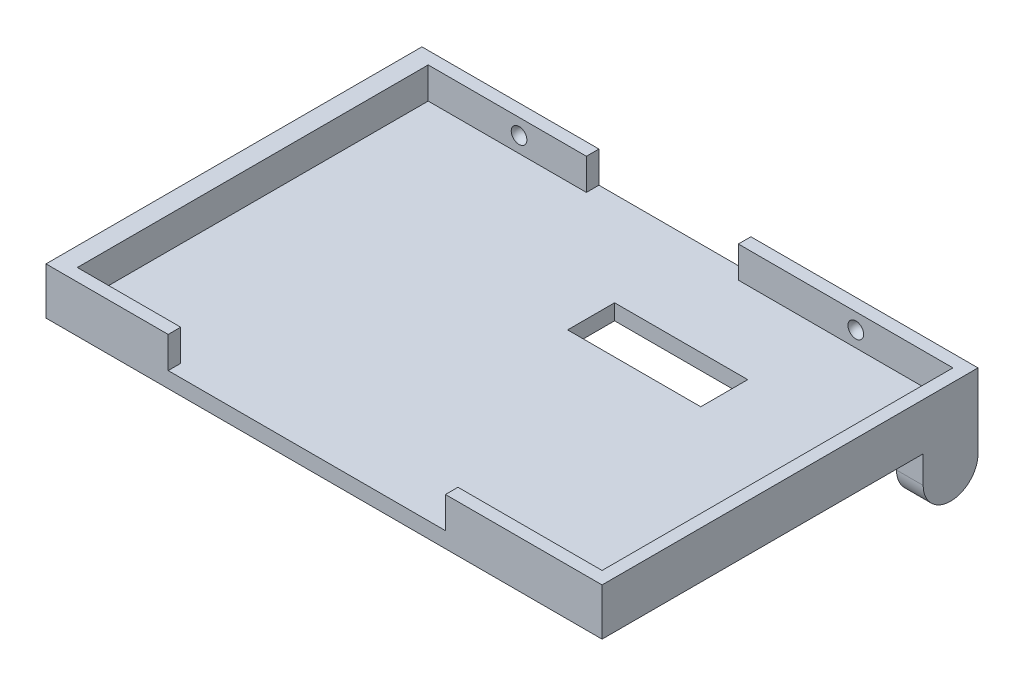
SolidWorks part; units mm, degrees
ref_plane "前视基准面" through (0, 0, 0) normal (0, 0, 1) x (1, 0, 0)
ref_plane "上视基准面" through (0, 0, 0) normal (0, 1, 0) x (1, 0, 0)
ref_plane "右视基准面" through (0, 0, 0) normal (1, 0, 0) x (0, 0, -1)
sketch "草图1" plane through (0, 0, 0) normal (0, 1, 0) x (1, 0, 0)
  line L1 (-17.75, 12) -> (17.75, 12)
  line L2 (-17.75, 12) -> (-17.75, -12)
  line L3 (-17.75, -12) -> (17.75, -12)
  line L4 (17.75, 12) -> (17.75, -12)
  line L5 (-17.75, 12) -> (17.75, -12) construction
  line L6 (-17.75, -12) -> (17.75, 12) construction
  point P0 (0, 0)
  dimension "D1" = 24
  dimension "D2" = 35.5
extrude "凸台-拉伸1" add sketch "草图1" along normal blind 3
sketch "草图2" plane through (0, 3, 0) normal (0, 1, 0) x (1, 0, 0)
  line L0 (17.75, 12) -> (-17.75, 12) construction
  line L1 (-15.75, 10) -> (15.75, 10)
  line L2 (-15.75, 10) -> (-15.75, -10)
  line L3 (-15.75, -10) -> (15.75, -10)
  line L4 (15.75, 10) -> (15.75, -10)
  line L5 (-15.75, 10) -> (15.75, -10) construction
  line L6 (-15.75, -10) -> (15.75, 10) construction
  line L7 (-17.75, 12) -> (-17.75, -12) construction
  point P0 (0, 0)
  dimension "D1" = 2
  dimension "D2" = 2
extrude "切除-拉伸1" cut sketch "草图2" against normal blind 2
sketch "草图4" plane through (0, 0, 0) normal (0, -1, 0) x (1, 0, 0)
  line L1 (-17.75, -12) -> (-16.05, -12)
  line L2 (-17.75, -12) -> (-17.75, -8.5)
  line L3 (-17.75, -8.5) -> (-16.05, -8.5)
  line L4 (-16.05, -12) -> (-16.05, -8.5)
  line L5 (17.75, -12) -> (16.05, -12)
  line L6 (17.75, -12) -> (17.75, -8.5)
  line L7 (17.75, -8.5) -> (16.05, -8.5)
  line L8 (16.05, -12) -> (16.05, -8.5)
  dimension "D1" = 3.5
  dimension "D2" = 1.7
  dimension "D3" = 1.7
  dimension "D4" = 3.5
extrude "凸台-拉伸2" add sketch "草图4" along normal blind 3.5
sketch "草图5" plane through (-17.75, 0, 0) normal (-1, 0, 0) x (0, 0, 1)
  line L1 (-12, 3) -> (-12, -3.5) construction
  line L2 (-12, -1.75) -> (-12, -3.5)
  line L5 (-10.25, -3.5) -> (-12, -3.5)
  arc A1 (-12, -1.75) -> (-10.25, -3.5) centre (-10.25, -1.75) ccw
  dimension "D1" = 1.75
extrude "切除-拉伸3" cut sketch "草图5" against normal blind 2
sketch "草图6" plane through (-17.75, 0, 0) normal (-1, 0, 0) x (0, 0, 1)
  line L0 (-8.5, -3.5) -> (-10.25, -3.5)
  line L1 (-8.5, -3.5) -> (-10.25, -3.5) construction
  line L2 (-8.5, -3.5) -> (-8.5, 0) construction
  line L3 (-8.5, -3.5) -> (-8.5, -1.75)
  arc A0 (-12, -1.75) -> (-10.25, -3.5) centre (-10.25, -1.75) ccw construction
  arc A1 (-10.25, -3.5) -> (-8.5, -1.75) centre (-10.25, -1.75) ccw
extrude "切除-拉伸4" cut sketch "草图6" against normal blind 2
sketch "草图7" plane through (17.75, 0, 0) normal (1, 0, 0) x (0, 0, -1)
  line L0 (8.5, -3.5) -> (10.25, -3.5)
  line L1 (12, -3.5) -> (8.5, -3.5) construction
  line L2 (8.5, -3.5) -> (8.5, 0) construction
  line L3 (8.5, -1.75) -> (8.5, -3.5)
  arc A0 (10.25, -3.5) -> (8.5, -1.75) centre (10.25, -1.75) cw
extrude "切除-拉伸5" cut sketch "草图7" against normal blind 2
sketch "草图8" plane through (17.75, 0, 0) normal (1, 0, 0) x (0, 0, -1)
  line L0 (12, -3.5) -> (10.25, -3.5)
  line L1 (12, 3) -> (12, -3.5) construction
  line L2 (12, -1.75) -> (12, -3.5)
  arc A0 (10.25, -3.5) -> (12, -1.75) centre (10.25, -1.75) ccw
extrude "切除-拉伸6" cut sketch "草图8" against normal blind 2
sketch "草图10" plane through (16.05, 0, 0) normal (-1, 0, 0) x (0, 0, 1)
  line L0 (-8.5, -1.75) -> (-8.5, 0) construction
  line L1 (12, 0) -> (-8.5, 0) construction
  circle A0 centre (-10.25, -1.75) radius 0.6
  dimension "D1" = 1.2
  dimension "D2" = 1.75
  dimension "D3" = 1.75
extrude "切除-拉伸8" cut sketch "草图10" against normal blind 1.5
sketch "草图11" plane through (0, 0, 0) normal (0, -1, 0) x (1, 0, 0)
  line L1 (0.55, -3) -> (9.05, -3)
  line L2 (0.55, -3) -> (0.55, -6)
  line L3 (0.55, -6) -> (9.05, -6)
  line L4 (9.05, -3) -> (9.05, -6)
  line L5 (16.05, -8.5) -> (16.05, -12) construction
  line L6 (16.05, -12) -> (-16.05, -12) construction
  dimension "D1" = 7
  dimension "D2" = 8.5
  dimension "D3" = 3
  dimension "D4" = 6
extrude "切除-拉伸9" cut sketch "草图11" against normal blind 2
sketch "草图12" plane through (-16.05, 0, 0) normal (1, 0, 0) x (0, 0, -1)
  line L0 (12, -1.75) -> (12, 0) construction
  line L1 (12, 0) -> (8.5, 0) construction
  circle A0 centre (10.25, -1.75) radius 0.6
  dimension "D1" = 1.2
  dimension "D2" = 1.75
  dimension "D3" = 1.75
extrude "切除-拉伸10" cut sketch "草图12" against normal blind 1.5
sketch "草图13" plane through (0, 3, 0) normal (0, 1, 0) x (1, 0, 0)
  line L1 (-15.6782, 11.2) -> (16.95, 11.2)
  line L2 (16.95, 11.2) -> (16.95, -11.2)
  line L3 (16.95, -11.2) -> (-15.75, -11.2)
  line L10 (17.75, -12) -> (17.75, 12) construction
  line L11 (-17.75, -12) -> (17.75, -12) construction
  line L12 (-15.6782, 11.2) -> (-16.55, 11.2)
  line L13 (-16.55, 11.2) -> (-16.55, -11.2)
  line L14 (-16.55, -11.2) -> (-15.75, -11.2)
  line L15 (-17.75, 12) -> (-17.75, -12) construction
  dimension "D1" = 1.2
  dimension "D2" = 0.8
  dimension "D3" = 0.8
extrude "切除-拉伸11" cut sketch "草图13" against normal blind 2
sketch "草图14" plane through (0, 0, -11.2) normal (0, 0, 1) x (1, 0, 0)
  line L0 (16.95, 1) -> (-16.55, 1) construction
  line L2 (-17.75, 3) -> (-17.75, -1.75) construction
  line L3 (-11.25, 2) -> (-10.25, 2)
  line L5 (10.25, 2) -> (11.25, 2)
  line L7 (17.75, 3) -> (17.75, -1.75) construction
  arc A2 (-11.25, 2) -> (-10.25, 2) centre (-10.75, 2) cw
  arc A3 (10.25, 2) -> (11.25, 2) centre (10.75, 2) cw
  dimension "D1" = 7
  dimension "D4" = 1
  dimension "D7" = 0.5
  dimension "D6" = 0.5
  dimension "D2" = 1
  dimension "D3" = 1
  dimension "D5" = 1
  dimension "D8" = 7
revolve "切除-旋转1" cut sketch "草图14" angle 360 about L5
sketch "草图15" plane through (0, 0, 11.2) normal (0, 0, -1) x (-1, 0, 0)
  line L0 (10.25, 2) -> (11.25, 2)
  line L1 (16.55, 1) -> (-16.95, 1) construction
  line L3 (-11.25, 2) -> (-10.25, 2)
  line L5 (-17.75, 3) -> (-17.75, 0) construction
  arc A2 (10.25, 2) -> (11.25, 2) centre (10.75, 2) cw
  arc A3 (-11.25, 2) -> (-10.25, 2) centre (-10.75, 2) cw
  dimension "D1" = 1
  dimension "D2" = 0.5
  dimension "D6" = 0.5
  dimension "D3" = 1
  dimension "D5" = 1
  dimension "D7" = 7
revolve "切除-旋转2" cut sketch "草图15" angle 360 about L3
sketch "草图16" plane through (16.05, 0, 0) normal (-1, 0, 0) x (0, 0, 1)
  line L1 (-10.5, -0.5) -> (-10, -0.5)
  line L2 (-8.5, -1.75) -> (-8.5, 0) construction
  arc A3 (-10.5, -0.5) -> (-10, -0.5) centre (-10.25, -0.5) cw
  circle A4 centre (-10.25, -1.75) radius 0.6 construction
  dimension "D4" = 0.25
  dimension "D1" = 0.5
  dimension "D2" = 1.75
  dimension "D3" = 1.25
revolve "切除-旋转3" cut sketch "草图16" angle 360 about L1
pattern_circular "阵列(圆周)3" count 8 over 360 about axis through (17.55, -1.75, -10.25) along (-1, 0, 0) of "切除-旋转3"
sketch "草图17" plane through (0, 3, 0) normal (0, 1, 0) x (1, 0, 0)
  line L0 (17.75, 12) -> (-17.75, 12) construction
  line L1 (16.95, 11.2) -> (-16.55, 11.2) construction
  line L2 (-6.45, 12) -> (3.25, 12)
  line L3 (-6.45, 12) -> (-6.45, 11.2)
  line L4 (-6.45, 11.2) -> (3.25, 11.2)
  line L5 (3.25, 12) -> (3.25, 11.2)
  line L6 (-17.75, 12) -> (-17.75, -12) construction
  line L7 (17.75, -12) -> (17.75, 12) construction
  dimension "D1" = 11.3
  dimension "D2" = 14.5
extrude "切除-拉伸12" cut sketch "草图17" against normal blind 2
sketch "草图18" plane through (0, 3, 0) normal (0, 1, 0) x (1, 0, 0)
  line L0 (-16.55, -11.2) -> (16.95, -11.2) construction
  line L1 (-9.95, -11.2) -> (7.75, -11.2)
  line L2 (-9.95, -11.2) -> (-9.95, -12)
  line L3 (-9.95, -12) -> (7.75, -12)
  line L4 (7.75, -11.2) -> (7.75, -12)
  line L5 (-17.75, -12) -> (17.75, -12) construction
  line L6 (-17.75, 12) -> (-17.75, -12) construction
  line L7 (17.75, -12) -> (17.75, 12) construction
  dimension "D1" = 7.8
  dimension "D2" = 10
extrude "切除-拉伸13" cut sketch "草图18" against normal blind 2
